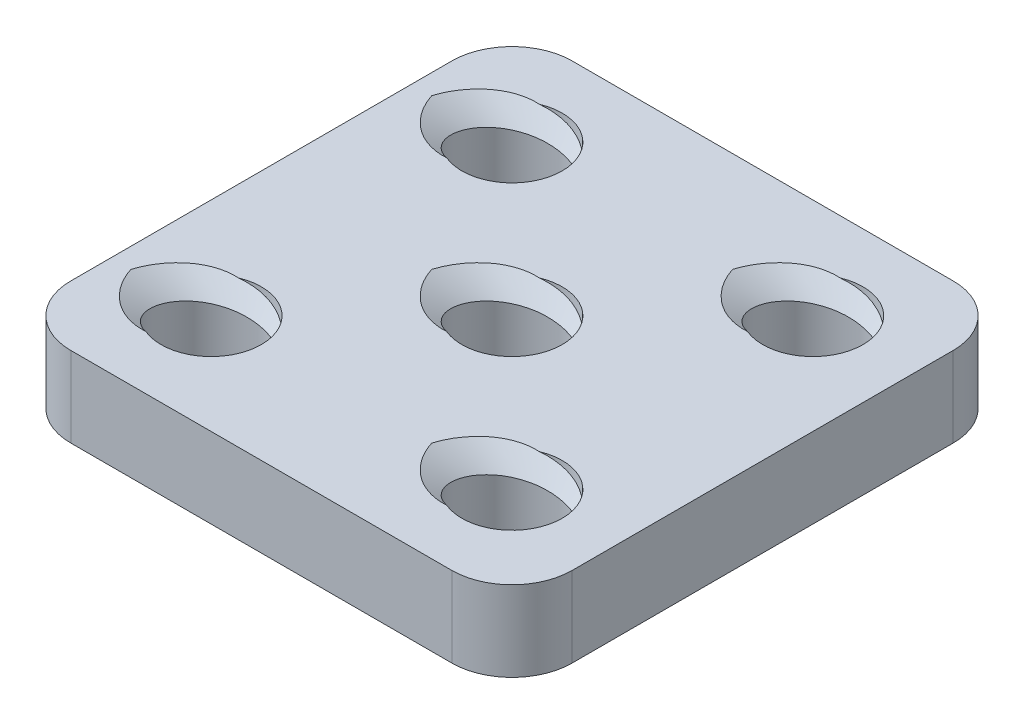
SolidWorks part; units mm, degrees
ref_plane "Front Plane" through (0, 0, 0) normal (0, 0, 1) x (1, 0, 0)
ref_plane "Top Plane" through (0, 0, 0) normal (0, 1, 0) x (1, 0, 0)
ref_plane "Right Plane" through (0, 0, 0) normal (1, 0, 0) x (0, 0, -1)
sketch "Sketch1" plane through (0, 0, 0) normal (0, 1, 0) x (1, 0, 0)
  line L1 (3, 0) -> (22, 0)
  line L2 (0, 3) -> (0, 22)
  line L3 (3, 25) -> (22, 25)
  line L4 (25, 3) -> (25, 22)
  arc A0 (3, 0) -> (0, 3) centre (3, 3) cw
  arc A1 (22, 0) -> (25, 3) centre (22, 3) ccw
  arc A2 (22, 25) -> (25, 22) centre (22, 22) cw
  arc A3 (0, 22) -> (3, 25) centre (3, 22) cw
  point P7 (0, 0)
  point P14 (0, 25)
  dimension "D2" = 3
  dimension "D1" = 25
extrude "Boss-Extrude1" add sketch "Sketch1" along normal blind 4
sketch "Sketch2" plane through (0, 4, 0) normal (0, 1, 0) x (1, 0, 0)
  line L0 (0, 22) -> (0, 3) construction
  line L1 (22, 25) -> (3, 25) construction
  line L2 (25, 3) -> (25, 22) construction
  line L3 (3, 0) -> (22, 0) construction
  circle A0 centre (5, 20) radius 2.5
  circle A1 centre (20, 20) radius 2.5
  circle A2 centre (5, 5) radius 2.5
  circle A3 centre (20, 5) radius 2.5
  circle A4 centre (12.5, 12.5) radius 2.5
  point P10 (0, 0)
  point P11 (0, 0)
  point P12 (0, 0)
  point P13 (0, 0)
  point P16 (0, 12.5)
  point P19 (12.5, 25)
  dimension "D5" = 5
  dimension "D1" = 5
  dimension "D2" = 5
  dimension "D3" = 5
  dimension "D4" = 5
extrude "Cut-Extrude1" cut sketch "Sketch2" against normal blind 4
sketch "Sketch4" plane through (0, 4, 0) normal (0, 1, 0) x (1, 0, 0)
  circle A0 centre (5, 20) radius 2.5 construction
  circle A1 centre (5, 20) radius 2.5
curve "Helix/Spiral1" pitch 4 height 4 radius 2.5 centre (5, 4, -20) axis (0, -1, 0) start towards (0, 0, 1)
sketch "Sketch5" plane through (0, 4, 0) normal (0, 1, 0) x (1, 0, 0)
  circle A0 centre (20, 20) radius 2.5 construction
  circle A1 centre (20, 20) radius 2.5
curve "Helix/Spiral2" pitch 4 height 4 radius 2.5 centre (20, 4, -20) axis (0, -1, 0) start towards (0, 0, 1)
ref_plane "Plane1" through (0, 0, -20) normal (0, 0, -1) x (-1, 0, 0)
sketch "Sketch6" plane through (0, 0, -20) normal (0, 0, -1) x (-1, 0, 0)
  line L21 (-2.5, 4) -> (-2.5, 4.75)
  line L22 (-2.5, 4) -> (-7.5, 4) construction
  line L23 (0, 4) -> (-3, 4) construction
  line L24 (-2.5, 4.75) -> (-1, 4)
  line L25 (-1, 4) -> (-2.5, 3.25)
  line L26 (-2.5, 3.25) -> (-2.5, 4)
  spline S4 degree 3 poles (-2.5, 4) (-2.5, 3.9172) (-2.6302, 3.7498) (-3.1862, 3.5001) (-4.0184, 3.25) (-5, 3) (-5.9816, 2.75) (-6.8138, 2.5) (-7.3698, 2.25) (-7.5651, 2) (-7.3698, 1.75) (-6.8138, 1.5) (-5.9816, 1.25) (-5, 1) (-4.0184, 0.75) (-3.1862, 0.4999) (-2.6302, 0.2502) (-2.5, 0.0828) (-2.5, 0) knots 0 0 0 0 0.0625 0.125 0.1875 0.25 0.3125 0.375 0.4375 0.5 0.5625 0.625 0.6875 0.75 0.8125 0.875 0.9375 1 1 1 1 construction
  dimension "D1" = 0.75
  dimension "D2" = 1.5
sweep "Cut-Sweep2" cut profiles "Sketch6" path "Helix/Spiral1" align with end faces yes
sketch "Sketch8" plane through (0, 0, -20) normal (0, 0, -1) x (-1, 0, 0)
  line L0 (-17.5, 4) -> (-17.5, 4.75)
  line L1 (-17.5, 4.75) -> (-16, 4)
  line L2 (-22, 4) -> (-3, 4) construction
  line L3 (-16, 4) -> (-17.5, 3.25)
  line L4 (-17.5, 3.25) -> (-17.5, 4)
  dimension "D1" = 0.75
  dimension "D2" = 1.5
sweep "Cut-Sweep3" cut profiles "Sketch8" path "Helix/Spiral2" align with end faces yes
ref_plane "Plane2" through (0, 0, -5) normal (0, 0, 1) x (1, 0, 0)
sketch "Sketch9" plane through (0, 4, 0) normal (0, 1, 0) x (1, 0, 0)
  circle A0 centre (5, 5) radius 2.5 construction
  circle A1 centre (5, 5) radius 2.5
curve "Helix/Spiral3" pitch 4 height 4 radius 2.5 centre (5, 4, -5) axis (0, -1, 0) start towards (0, 0, 1)
sketch "Sketch10" plane through (0, 4, 0) normal (0, 1, 0) x (1, 0, 0)
  circle A0 centre (20, 5) radius 2.5 construction
  circle A1 centre (20, 5) radius 2.5
curve "Helix/Spiral4" pitch 4 height 4 radius 2.5 centre (20, 4, -5) axis (0, -1, 0) start towards (0, 0, 1)
sketch "Sketch11" plane through (0, 0, -5) normal (0, 0, 1) x (1, 0, 0)
  line L15 (2.5, 4) -> (2.5, 3.25)
  line L16 (2.5, 4) -> (2.5, 4.75)
  line L17 (2.5, 4.75) -> (1, 4)
  line L18 (3, 4) -> (0, 4) construction
  line L19 (1, 4) -> (2.5, 3.25)
  dimension "D1" = 0.75
  dimension "D2" = 1.5
sweep "Cut-Sweep5" cut profiles "Sketch11" path "Helix/Spiral3" align with end faces yes
sketch "Sketch12" plane through (0, 0, -5) normal (0, 0, 1) x (1, 0, 0)
  line L0 (17.5, 4) -> (17.5, 4.75)
  line L1 (17.5, 4) -> (17.5, 3.25)
  line L2 (17.5, 4.75) -> (16, 4)
  line L3 (3, 4) -> (22, 4) construction
  line L4 (16, 4) -> (17.5, 3.25)
  dimension "D1" = 0.75
  dimension "D2" = 1.5
sweep "Cut-Sweep6" cut profiles "Sketch12" path "Helix/Spiral4" align with end faces yes
ref_plane "Plane3" through (0, 0, -12.5) normal (0, 0, 1) x (1, 0, 0)
sketch "Sketch13" plane through (0, 4, 0) normal (0, 1, 0) x (1, 0, 0)
  circle A0 centre (12.5, 12.5) radius 2.5 construction
  circle A1 centre (12.5, 12.5) radius 2.5
curve "Helix/Spiral5" pitch 4 height 4 radius 2.5 centre (12.5, 4, -12.5) axis (0, -1, 0) start towards (0, 0, 1)
sketch "Sketch14" plane through (0, 0, -12.5) normal (0, 0, 1) x (1, 0, 0)
  line L0 (10, 4) -> (10, 4.75)
  line L1 (15, 4) -> (10, 4) construction
  line L2 (10, 4) -> (10, 3.25)
  line L3 (10, 4.75) -> (8.5, 4)
  line L4 (7.5, 4) -> (4.0459, 4) construction
  line L5 (8.5, 4) -> (10, 3.25)
  spline S0 degree 3 poles (10, 4) (10, 3.9172) (10.1302, 3.7498) (10.6862, 3.5001) (11.5184, 3.25) (12.5, 3) (13.4816, 2.75) (14.3138, 2.5) (14.8698, 2.25) (15.0651, 2) (14.8698, 1.75) (14.3138, 1.5) (13.4816, 1.25) (12.5, 1) (11.5184, 0.75) (10.6862, 0.4999) (10.1302, 0.2502) (10, 0.0828) (10, 0) knots 0 0 0 0 0.0625 0.125 0.1875 0.25 0.3125 0.375 0.4375 0.5 0.5625 0.625 0.6875 0.75 0.8125 0.875 0.9375 1 1 1 1 construction
  dimension "D1" = 0.75
  dimension "D2" = 1.5
sweep "Cut-Sweep7" cut profiles "Sketch14" path "Helix/Spiral5" align with end faces yes
